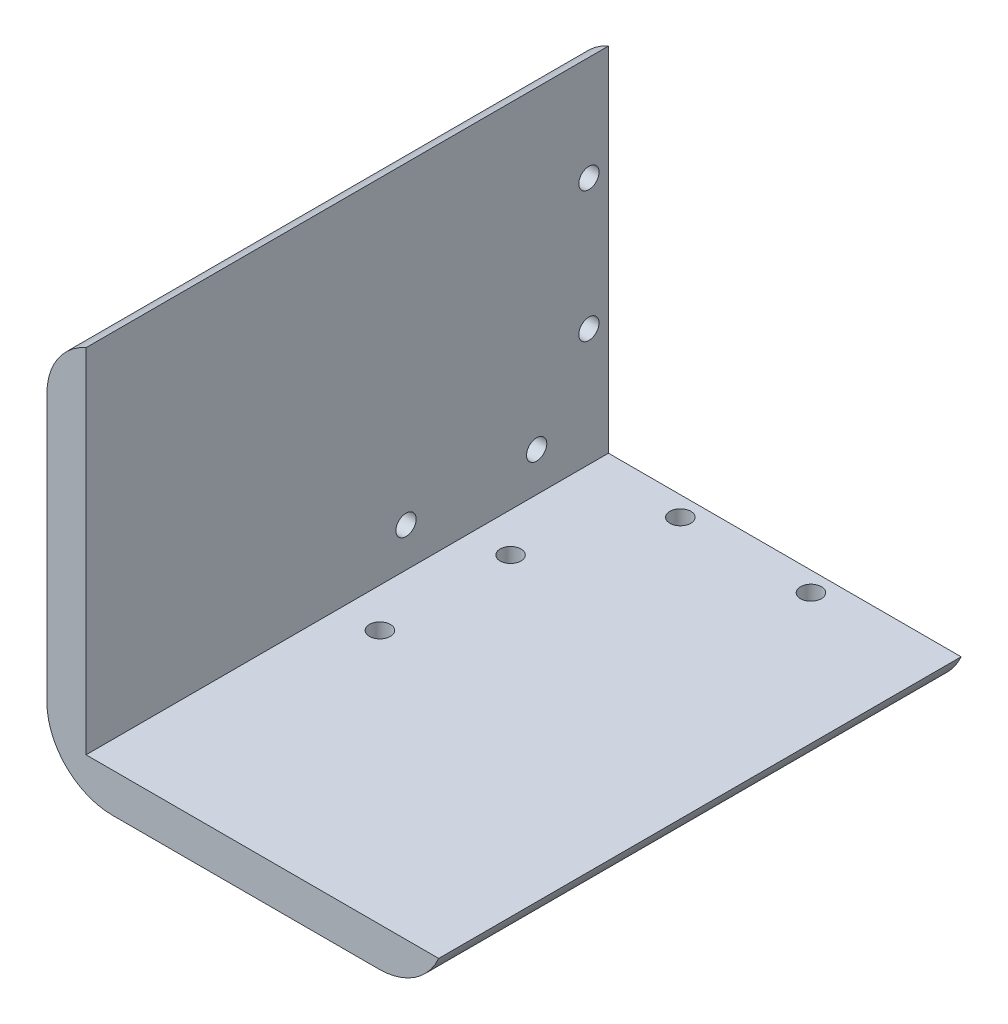
SolidWorks part; units mm, degrees
ref_plane "前视基准面" through (0, 0, 0) normal (0, 0, 1) x (1, 0, 0)
ref_plane "上视基准面" through (0, 0, 0) normal (0, 1, 0) x (1, 0, 0)
ref_plane "右视基准面" through (0, 0, 0) normal (1, 0, 0) x (0, 0, -1)
other "Configuration Table"
sketch "草图1" plane through (0, 0, 0) normal (0, 0, 1) x (1, 0, 0)
  line L0 (0, 0) -> (0, 60)
  line L1 (0, 60) -> (6, 60)
  line L2 (6, 60) -> (6, 6)
  line L3 (6, 6) -> (60, 6)
  line L4 (60, 6) -> (60, 0)
  line L5 (60, 0) -> (0, 0)
  dimension "D1" = 6
  dimension "D2" = 6
  dimension "D3" = 60
  dimension "D4" = 60
extrude "凸台-拉伸1" add sketch "草图1" along normal mid plane 80
fillet "圆角1" radius 10 3 edges at (0, 60, 0) (60, 0, 0) (0, 0, 0)
sketch "草图3" plane through (0, 0, 0) normal (-1, 0, 0) x (0, 0, 1)
  line L0 (-29, 12) -> (-9, 12) construction
  line L1 (40, 0) -> (-40, 0) construction
  line L2 (-40, 50.8348) -> (-40, 10) construction
  circle A0 centre (-37, 44) radius 1.55
  circle A1 centre (-37, 24) radius 1.55
  circle A2 centre (-29, 12) radius 1.55
  circle A3 centre (-9, 12) radius 1.55
  dimension "D1" = 3.1
  dimension "D7" = 11
  dimension "D2" = 20
  dimension "D3" = 44
  dimension "D4" = 3
  dimension "D5" = 20
  dimension "D6" = 12
extrude "切除-拉伸1" cut sketch "草图3" against normal through all
sketch "草图4" plane through (0, 6, 0) normal (0, 1, 0) x (1, 0, 0)
  line L0 (12, 19) -> (12, -1) construction
  line L1 (60, 40) -> (6, 40) construction
  circle A0 centre (12, -1) radius 1.6
  circle A1 centre (12, 19) radius 1.6
  dimension "D1" = 12
  dimension "D3" = 3.2
  dimension "D2" = 21
  dimension "D4" = 20
extrude "切除-拉伸2" cut sketch "草图4" against normal through all
sketch "草图5" plane through (0, 0, 0) normal (0, -1, 0) x (1, 0, 0)
  line L0 (20, -37) -> (40, -37) construction
  line L1 (10, -40) -> (50.8348, -40) construction
  line L2 (6, 40) -> (6, -40) construction
  circle A0 centre (20, -37) radius 1.6
  circle A1 centre (40, -37) radius 1.6
  dimension "D1" = 3.2
  dimension "D2" = 3
  dimension "D3" = 20
  dimension "D4" = 14
extrude "切除-拉伸3" cut sketch "草图5" against normal through all
